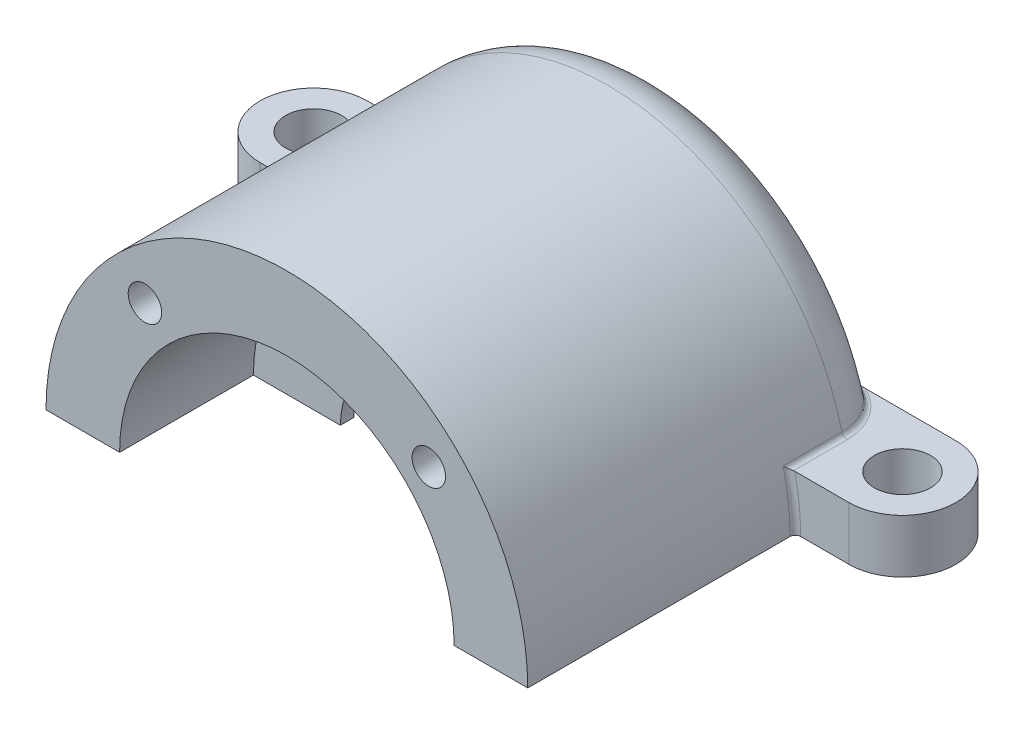
SolidWorks part; units mm, degrees
material "2024 Сплав"
ref_plane "Спереди" through (0, 0, 0) normal (0, 0, 1) x (1, 0, 0)
ref_plane "Сверху" through (0, 0, 0) normal (0, 1, 0) x (1, 0, 0)
ref_plane "Справа" through (0, 0, 0) normal (1, 0, 0) x (0, 0, -1)
sketch "Эскиз1" plane through (0, 0, 0) normal (0, 1, 0) x (1, 0, 0)
  line L0 (-12.5, 0) -> (-12.5, 10)
  line L1 (-12.5, 10) -> (-6, 10)
  line L4 (-18, 28) -> (-18, 0)
  line L5 (-18, 0) -> (-12.5, 0)
  line L7 (-18, 28) -> (-11, 28)
  line L9 (-11, 28) -> (-11, 14)
  line L10 (0, 0) -> (0, 50000) construction
  line L12 (-7.5, 11) -> (-7.5, 14)
  line L13 (-7.5, 14) -> (-11, 14)
  line L15 (-6, 10) -> (-6, 11)
  line L16 (-6, 11) -> (-7.5, 11)
  dimension "D1" = 12.5
  dimension "D2" = 18
  dimension "D3" = 10
  dimension "D4" = 7.5
  dimension "D5" = 28
  dimension "D6" = 4
  dimension "D7" = 11
  dimension "D8" = 1
  dimension "D9" = 6
revolve "Повернуть1" add sketch "Эскиз1" angle 180 about L10
sketch "Эскиз2" plane through (0, 0, 0) normal (0, 1, 0) x (1, 0, 0)
  line L5 (11, 28) -> (22, 28)
  line L6 (11, 28) -> (11, 20)
  line L8 (11, 20) -> (22, 20)
  arc A1 (22, 28) -> (22, 20) centre (22, 24) cw
  dimension "D1" = 11
  dimension "D2" = 8
extrude "Бобышка-Вытянуть1" add sketch "Эскиз2" along normal blind 4
sketch "Эскиз3" plane through (0, 4, 0) normal (0, 1, 0) x (1, 0, 0)
  circle A0 centre (22, 24) radius 2.1
  arc A1 (22, 20) -> (22, 28) centre (22, 24) ccw construction
  dimension "D1" = 4.2
extrude "Вырез-Вытянуть1" cut sketch "Эскиз3" against normal up to next
mirror "Зеркальное отражение1" about plane through (0, 0, 0) normal (1, 0, 0) of "Вырез-Вытянуть1", "Бобышка-Вытянуть1"
sketch "Эскиз4" plane through (0, 0, -10) normal (0, 0, 1) x (1, 0, 0)
  line L0 (0, 0) -> (12.5, 0) construction
  circle A0 centre (4.75, 8.2272) radius 1.1
  dimension "D2" = 2.2
  dimension "D1" = 9.5
  dimension "D3" = 60
extrude "Вырез-Вытянуть2" cut sketch "Эскиз4" against normal up to next
sketch "Эскиз5" plane through (0, 0, -10) normal (0, 0, 1) x (1, 0, 0)
  circle A0 centre (4.75, 8.2272) radius 1.9
  dimension "D1" = 3.8
extrude "Вырез-Вытянуть3" cut sketch "Эскиз5" against normal blind 0.5
sketch "Эскиз6" plane through (0, 0, -10.5) normal (0, 0, 1) x (1, 0, 0)
  circle A0 centre (4.75, 8.2272) radius 1.9
  dimension "D1" = 3.8
extrude "Вырез-Вытянуть4" cut sketch "Эскиз6" against normal blind 1.2 draft 45
pattern_circular "Круговой массив1" count 2 every 60 about axis through (0, 0, 0) along (0, 0, 1) of "Вырез-Вытянуть2", "Вырез-Вытянуть3", "Вырез-Вытянуть4"
hole_wizard "Сверление под метчик M31" positions "Трехмерный эскиз1" profile "Эскиз7" hole size "M3" standard "ISO"
sketch3d "Трехмерный эскиз1"
  line L0 (0, 0, 0) -> (18, 0, 0) construction
  point P0 (10.6066, 10.6066, 0)
  dimension "D1" = 15
  dimension "D2" = 45
sketch "Эскиз7" plane through (10.6066, 10.6066, 0) normal (1, 0, 0) x (0, -1, 0)
  line L0 (0, 0) -> (0, 15.7511)
  line L1 (0, 15.7511) -> (1.25, 15)
  line L2 (1.25, 15) -> (1.25, 0)
  line L5 (1.25, 0) -> (0, 0)
  line L10 (0, 15.7511) -> (-1.25, 15) construction
  line L11 (0, -6.35) -> (0, 107.95) construction
  dimension "Диаметр отверстия" = 2.5
  dimension "Глубина отверстия" = 15
  dimension "Угол заточки сверла" = 118
cosmetic thread "Условное изображение резьбы1" parameters "D2"=3
pattern_circular "Круговой массив2" count 2 every 90 about axis through (0, 0, 0) along (0, 0, 1) of "Сверление под метчик M31"
fillet "Скругление1" radius 4 1 edges at (0, 18, -28)
fillet "Скругление2" radius 0.4 6 edges at (-16.6901, 4, -26.4489) (16.0762, 4, -27.0682) (-17.8871, 2.0126, -20) (-17.5499, 4, -22) (17.5499, 4, -22) (17.8871, 2.0126, -20)
